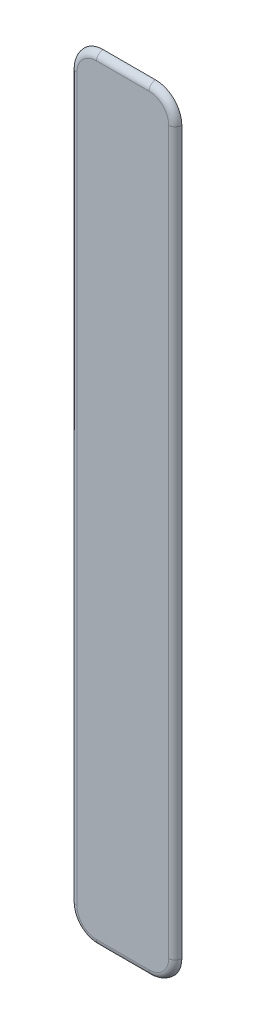
SolidWorks part; units mm, degrees
ref_plane "Спереди" through (0, 0, 0) normal (0, 0, 1) x (1, 0, 0)
ref_plane "Сверху" through (0, 0, 0) normal (0, 1, 0) x (1, 0, 0)
ref_plane "Справа" through (0, 0, 0) normal (1, 0, 0) x (0, 0, -1)
sketch "Эскиз1" plane through (0, 0, 0) normal (0, 0, 1) x (1, 0, 0)
  line L1 (0, 0) -> (16, 0)
  line L2 (0, 0) -> (0, 118)
  line L3 (0, 118) -> (16, 118)
  line L4 (16, 0) -> (16, 118)
  dimension "D1" = 16
  dimension "D2" = 118
extrude "Бобышка-Вытянуть1" add sketch "Эскиз1" along normal blind 1
fillet "Скругление1" radius 4 4 edges at (0, 0, 0.5) (16, 0, 0.5) (0, 118, 0.5) (16, 118, 0.5)
fillet "Скругление2" radius 1 8 edges at (1.1716, 116.8284, 1) (8, 118, 1) (14.8284, 116.8284, 1) (16, 59, 1) (14.8284, 1.1716, 1) (8, 0, 1) (1.1716, 1.1716, 1) (0, 59, 1)
